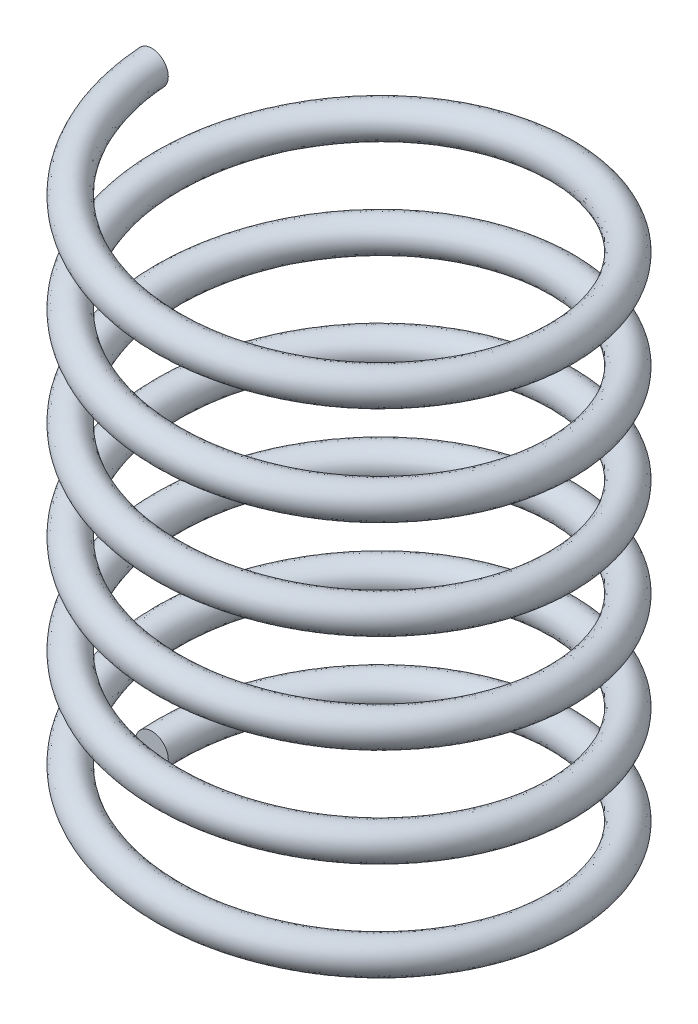
SolidWorks part; units mm, degrees
note: '?' marks a value the reader was unsure of.
ref_plane "Front" through (0, 0, 0) normal (0, 0, 1) x (1, 0, 0)
ref_plane "Top" through (0, 0, 0) normal (0, 1, 0) x (1, 0, 0)
ref_plane "Right" through (0, 0, 0) normal (1, 0, 0) x (0, 0, -1)
sketch "Sketch5" plane through (0, 0, 0) normal (0, 1, 0) x (1, 0, 0)
  circle A0 centre (0, 0) radius 4.7625
  dimension "D1" = 9.525
curve "Helix2" pitch 2.3813 height 14.2875 turns 6
sketch "Sketch3" plane through (0, 0, 0) normal (0, 0, 1) x (1, 0, 0)
  circle A0 centre (-4.7625, 0) radius 0.3969
  dimension "D1" = 0.7937
sweep "Sweep1" add profiles "Sketch3" path "Helix2"
ref_axis "Axis1" through (0, 50, 0) along (0, -1, 0)?
